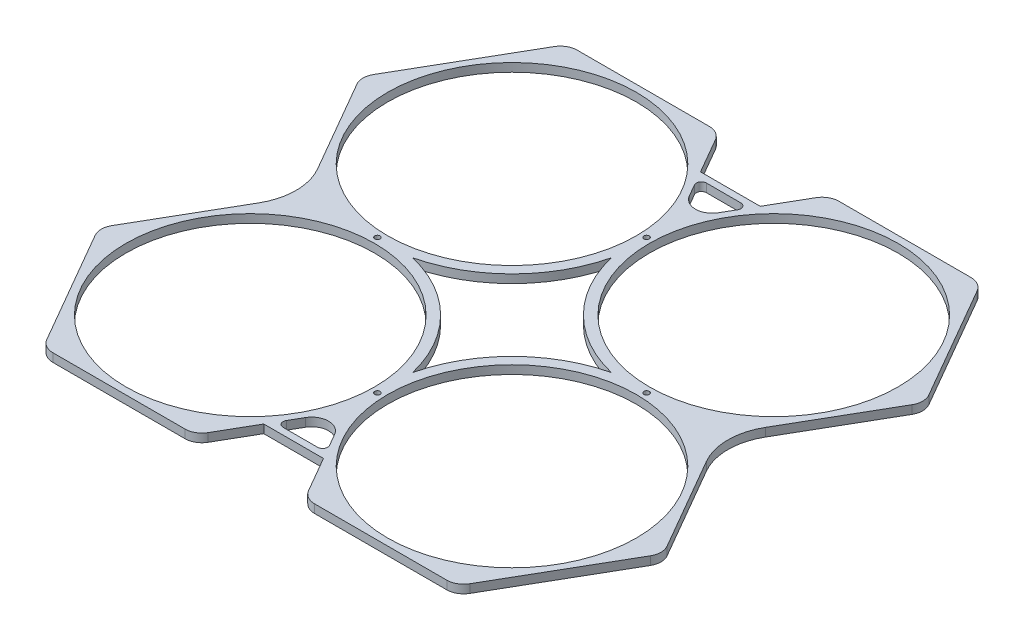
SolidWorks part; units mm, degrees
ref_plane "前视基准面" through (0, 0, 0) normal (0, 0, 1) x (1, 0, 0)
ref_plane "上视基准面" through (0, 0, 0) normal (0, 1, 0) x (1, 0, 0)
ref_plane "右视基准面" through (0, 0, 0) normal (1, 0, 0) x (0, 0, -1)
other "Configuration Table"
sketch "草图1" plane through (0, 0, 0) normal (0, 1, 0) x (1, 0, 0)
  line L0 (-40.28, 0) -> (40.28, 0) construction
  line L1 (-40.28, -50) -> (40.28, -50)
  line L2 (-40.28, -50) -> (-40.28, 50)
  line L3 (-40.28, 50) -> (40.28, 50)
  line L4 (40.28, -50) -> (40.28, 50)
  line L5 (-40.28, -50) -> (40.28, 50) construction
  line L6 (-40.28, 50) -> (40.28, -50) construction
  line L7 (0, -50) -> (0, 50) construction
  line L8 (-40.28, -50) -> (-40.28, -75.1) construction
  line L9 (-40.28, -75.1) -> (40.28, -75.1) construction
  line L10 (40.28, -75.1) -> (40.28, -50) construction
  line L11 (0, -50) -> (0, -75.1) construction
  line L12 (-40.28, -62.55) -> (40.28, -62.55) construction
  line L13 (-27, -75.1) -> (27, -75.1)
  line L14 (27, -75.1) -> (27, -50)
  line L15 (-27, -75.1) -> (-27, -50)
  circle A0 centre (-34.12, 46.89) radius 1.6
  circle A1 centre (15.09, 46.89) radius 1.6
  circle A2 centre (15.09, -40.19) radius 1.6
  circle A3 centre (-34.12, -40.19) radius 1.6
  circle A5 centre (-15.25, 15.25) radius 1.6
  circle A6 centre (15.25, 15.25) radius 1.6
  circle A7 centre (15.25, -15.25) radius 1.6
  circle A8 centre (-15.25, -15.25) radius 1.6
  circle A9 centre (14, -62.55) radius 1.6
  circle A10 centre (-14, -62.55) radius 1.6
  point P0 (0, 0)
  point P19 (0, 0)
  point P22 (0, 0)
  point P40 (0, -75.1)
  dimension "D3" = 3.2
  dimension "D10" = 3.2
  dimension "D11" = 30.5
  dimension "D12" = 30.5
  dimension "D14" = 3.2
  dimension "D1" = 80.56
  dimension "D2" = 100
  dimension "D4" = 6.16
  dimension "D5" = 3.11
  dimension "D8" = 49.21
  dimension "D9" = 87.08
  dimension "D13" = 25.1
  dimension "D15" = 28
  dimension "D16" = 54
  dimension "D6" = 2
  dimension "D7" = 2
sketch "草图6" plane through (0, 0, 0) normal (0, 1, 0) x (1, 0, 0)
  line L0 (0, 0) -> (50000, 0) construction
  line L1 (0, 0) -> (0, 50000) construction
  line L2 (-77.7817, 77.7817) -> (77.7817, 77.7817) construction
  line L3 (77.7817, 77.7817) -> (77.7817, -77.7817) construction
  line L4 (69.7817, 77.7817) -> (85.7817, 77.7817) construction
  line L5 (77.7817, 69.7817) -> (77.7817, 85.7817) construction
  line L6 (-77.7817, -77.7817) -> (77.7817, 77.7817) construction
  line L7 (77.7817, 91.5317) -> (64.0317, 77.7817)
  line L8 (91.5317, 77.7817) -> (77.7817, 64.0317)
  line L9 (-70.9067, 64.0317) -> (-40.28, 33.405)
  line L10 (-91.5317, -91.5317) -> (88.3498, 88.3498) construction
  line L11 (-87.5951, 87.5951) -> (77.7817, -77.7817) construction
  line L12 (40.28, -50) -> (40.28, 50)
  line L13 (40.28, 50) -> (-40.28, 50)
  line L14 (-40.28, 50) -> (-40.28, -50)
  line L15 (-40.28, -50) -> (40.28, -50)
  line L16 (-77.7817, 64.0317) -> (-70.9067, 64.0317)
  line L17 (-91.5317, 77.7817) -> (-77.7817, 64.0317)
  line L18 (-91.5317, 77.7817) -> (-91.5317, 85.1678)
  line L19 (-85.1678, 91.5317) -> (-91.5317, 85.1678)
  line L20 (-77.7817, 91.5317) -> (-85.1678, 91.5317)
  line L21 (77.7817, 91.5317) -> (85.1678, 91.5317)
  line L22 (91.5317, 77.7817) -> (91.5317, 85.1678)
  line L23 (-77.7817, 91.5317) -> (-64.0317, 77.7817)
  line L24 (-64.0317, 77.7817) -> (-64.0317, 70.9067)
  line L25 (72.1249, 83.4386) -> (83.4386, 72.1249) construction
  line L26 (77.7817, 64.0317) -> (70.9067, 64.0317)
  line L27 (64.0317, 77.7817) -> (64.0317, 70.9067)
  line L28 (77.7817, 64.0317) -> (70.9067, 64.0317)
  line L29 (64.0317, 77.7817) -> (64.0317, 70.9067)
  line L30 (64.0317, 70.9067) -> (40.28, 47.155)
  line L31 (70.9067, 64.0317) -> (40.28, 33.405)
  line L32 (85.1678, 91.5317) -> (91.5317, 85.1678)
  line L33 (-64.0317, 70.9067) -> (-40.28, 47.155)
  line L34 (-64.0317, -70.9067) -> (-40.28, -47.155)
  line L35 (-64.0317, -77.7817) -> (-64.0317, -70.9067)
  line L36 (-77.7817, -91.5317) -> (-64.0317, -77.7817)
  line L37 (-77.7817, -91.5317) -> (-85.1678, -91.5317)
  line L38 (-85.1678, -91.5317) -> (-91.5317, -85.1678)
  line L39 (-91.5317, -77.7817) -> (-91.5317, -85.1678)
  line L40 (-91.5317, -77.7817) -> (-77.7817, -64.0317)
  line L41 (-77.7817, -64.0317) -> (-70.9067, -64.0317)
  line L42 (-70.9067, -64.0317) -> (-40.28, -33.405)
  line L43 (70.9067, -64.0317) -> (40.28, -33.405)
  line L44 (77.7817, -64.0317) -> (70.9067, -64.0317)
  line L45 (91.5317, -77.7817) -> (77.7817, -64.0317)
  line L46 (91.5317, -77.7817) -> (91.5317, -85.1678)
  line L47 (85.1678, -91.5317) -> (91.5317, -85.1678)
  line L48 (77.7817, -91.5317) -> (85.1678, -91.5317)
  line L49 (77.7817, -91.5317) -> (64.0317, -77.7817)
  line L50 (64.0317, -77.7817) -> (64.0317, -70.9067)
  line L51 (64.0317, -70.9067) -> (40.28, -47.155)
  circle A0 centre (-77.7817, 77.7817) radius 65.9 construction
  circle A1 centre (77.7817, 77.7817) radius 65.9 construction
  circle A2 centre (-77.7817, -77.7817) radius 65.9 construction
  circle A3 centre (77.7817, -77.7817) radius 65.9 construction
  circle A4 centre (0, 0) radius 110 construction
  circle A5 centre (77.7817, 77.7817) radius 8 construction
  circle A6 centre (77.7817, 85.7817) radius 1.5
  circle A7 centre (85.7817, 77.7817) radius 1.5
  circle A8 centre (77.7817, 69.7817) radius 1.5
  circle A9 centre (69.7817, 77.7817) radius 1.5
  circle A10 centre (77.7817, 77.7817) radius 13.75 construction
  circle A11 centre (-77.7817, 85.7817) radius 1.5
  circle A12 centre (-85.7817, 77.7817) radius 1.5
  circle A13 centre (-69.7817, 77.7817) radius 1.5
  circle A14 centre (-77.7817, 69.7817) radius 1.5
  circle A15 centre (-77.7817, -69.7817) radius 1.5
  circle A16 centre (-69.7817, -77.7817) radius 1.5
  circle A17 centre (-85.7817, -77.7817) radius 1.5
  circle A18 centre (-77.7817, -85.7817) radius 1.5
  circle A19 centre (77.7817, -85.7817) radius 1.5
  circle A20 centre (85.7817, -77.7817) radius 1.5
  circle A21 centre (69.7817, -77.7817) radius 1.5
  circle A22 centre (77.7817, -69.7817) radius 1.5
  point P18 (77.7817, 77.7817)
  point P21 (77.7817, 77.7817)
  point P24 (0, 0)
  point P31 (77.7817, 77.7817)
  point P77 (77.7817, 77.7817)
sketch "草图7" plane through (0, 0, 0) normal (0, 1, 0) x (1, 0, 0)
  line L0 (0, 0) -> (50000, 0) construction
  line L1 (0, 0) -> (0, 50000) construction
  line L2 (17.7373, 129.7817) -> (-17.7373, 129.7817)
  line L3 (164.9616, 82.7817) -> (125.7018, 150.7817)
  line L4 (117.0416, 155.7817) -> (38.5219, 155.7817)
  line L5 (29.8617, 150.7817) -> (17.7373, 129.7817)
  line L8 (133.0447, 17.5) -> (164.9616, 72.7817)
  line L9 (32.7484, -0.2183) -> (122.8151, -0.2183) [skipped]
  line L10 (0, 56.5037) -> (32.7484, -0.2183) [skipped]
  line L11 (10.2318, 125.7817) -> (-10.2318, 125.7817)
  line L12 (12.8298, 121.2817) -> (8.6603, 114.0598)
  line L13 (-133.0447, 17.5) -> (-164.9616, 72.7817)
  line L14 (-164.9616, 82.7817) -> (-125.7018, 150.7817)
  line L15 (-117.0416, 155.7817) -> (-38.5219, 155.7817)
  line L16 (-29.8617, 150.7817) -> (-17.7373, 129.7817)
  line L17 (-12.8298, 121.2817) -> (-8.6603, 114.0598)
  line L18 (164.9616, -82.7817) -> (125.7018, -150.7817)
  line L19 (117.0416, -155.7817) -> (38.5219, -155.7817)
  line L20 (29.8617, -150.7817) -> (17.7373, -129.7817)
  line L21 (12.8298, -121.2817) -> (8.6603, -114.0598)
  line L22 (-12.8298, -121.2817) -> (-8.6603, -114.0598)
  line L23 (10.2318, -125.7817) -> (-10.2318, -125.7817)
  line L24 (17.7373, -129.7817) -> (-17.7373, -129.7817)
  line L25 (-29.8617, -150.7817) -> (-17.7373, -129.7817)
  line L26 (-117.0416, -155.7817) -> (-38.5219, -155.7817)
  line L27 (-164.9616, -82.7817) -> (-125.7018, -150.7817)
  line L28 (-133.0447, -17.5) -> (-164.9616, -72.7817)
  line L29 (133.0447, -17.5) -> (164.9616, -72.7817)
  line L30 (-19.75, 22.75) -> (19.75, 22.75) construction
  line L31 (-15.25, -15.25) -> (15.25, -15.25) construction
  line L32 (-15.25, -15.25) -> (-15.25, 15.25) construction
  line L33 (-15.25, 15.25) -> (15.25, 15.25) construction
  line L34 (15.25, -15.25) -> (15.25, 15.25) construction
  line L35 (-15.25, -15.25) -> (15.25, 15.25) construction
  line L36 (-15.25, 15.25) -> (15.25, -15.25) construction
  line L37 (22.75, -19.75) -> (22.75, 19.75) construction
  line L38 (-19.75, -22.75) -> (19.75, -22.75) construction
  line L39 (-22.75, -19.75) -> (-22.75, 19.75) construction
  line L40 (-22.75, 22.75) -> (22.75, 22.75) construction
  line L41 (22.75, -22.75) -> (22.75, 22.75) construction
  line L42 (-22.75, -22.75) -> (-22.75, 22.75) construction
  line L43 (-22.75, -22.75) -> (22.75, -22.75) construction
  circle A0 centre (77.7817, 77.7817) radius 78 construction
  arc A1 (164.9616, 82.7817) -> (164.9616, 72.7817) centre (156.3014, 77.7817) cw
  arc A2 (125.7018, 150.7817) -> (117.0416, 155.7817) centre (117.0416, 145.7817) ccw
  circle A3 centre (77.7817, 77.7817) radius 65.9 construction
  circle A7 centre (77.7817, 77.7817) radius 65.9 construction
  circle A8 centre (77.7817, 77.7817) radius 73.9
  arc A9 (38.5219, 155.7817) -> (29.8617, 150.7817) centre (38.5219, 145.7817) ccw
  arc A10 (133.0447, 17.5) -> (128.3556, 0) centre (163.3556, 0) ccw construction
  arc A11 (133.0447, 17.5) -> (133.0447, -17.5) centre (163.3556, 0) ccw
  circle A12 centre (0, 119.0598) radius 10 construction
  arc A13 (8.6603, 114.0598) -> (-8.6603, 114.0598) centre (0, 119.0598) cw
  circle A14 centre (-77.7817, 77.7817) radius 73.9
  arc A15 (-133.0447, 17.5) -> (-133.0447, -17.5) centre (-163.3556, 0) cw
  arc A16 (-164.9616, 82.7817) -> (-164.9616, 72.7817) centre (-156.3014, 77.7817) ccw
  arc A17 (-125.7018, 150.7817) -> (-117.0416, 155.7817) centre (-117.0416, 145.7817) cw
  arc A18 (-38.5219, 155.7817) -> (-29.8617, 150.7817) centre (-38.5219, 145.7817) cw
  circle A19 centre (-77.7817, -77.7817) radius 73.9
  circle A20 centre (77.7817, -77.7817) radius 73.9
  arc A21 (164.9616, -82.7817) -> (164.9616, -72.7817) centre (156.3014, -77.7817) ccw
  arc A22 (125.7018, -150.7817) -> (117.0416, -155.7817) centre (117.0416, -145.7817) cw
  arc A23 (8.6603, -114.0598) -> (-8.6603, -114.0598) centre (0, -119.0598) ccw
  arc A24 (-38.5219, -155.7817) -> (-29.8617, -150.7817) centre (-38.5219, -145.7817) ccw
  arc A25 (-125.7018, -150.7817) -> (-117.0416, -155.7817) centre (-117.0416, -145.7817) ccw
  arc A26 (-164.9616, -82.7817) -> (-164.9616, -72.7817) centre (-156.3014, -77.7817) cw
  arc A27 (300.0616, 4.7817) -> (300.0616, -5.2183) centre (291.4013, -0.2183) cw
  arc A28 (38.5219, -155.7817) -> (29.8617, -150.7817) centre (38.5219, -145.7817) cw
  arc A29 (-12.8298, -121.2817) -> (-10.2318, -125.7817) centre (-10.2318, -122.7817) ccw
  arc A30 (10.2318, 125.7817) -> (12.8298, 121.2817) centre (10.2318, 122.7817) cw
  arc A31 (-12.8298, 121.2817) -> (-10.2318, 125.7817) centre (-10.2318, 122.7817) cw
  arc A32 (12.8298, -121.2817) -> (10.2318, -125.7817) centre (10.2318, -122.7817) cw
  arc A33 (19.75, 22.75) -> (22.75, 19.75) centre (19.75, 19.75) cw construction
  arc A34 (-19.75, 22.75) -> (-22.75, 19.75) centre (-19.75, 19.75) ccw construction
  arc A35 (-19.75, -22.75) -> (-22.75, -19.75) centre (-19.75, -19.75) cw construction
  arc A36 (22.75, -19.75) -> (19.75, -22.75) centre (19.75, -19.75) cw construction
  point P4 (77.7817, 155.7817)
  point P21 (167.8484, 77.7817)
  point P26 (0, 0)
  point P27 (-33.5219, 154.442)
  point P33 (0, 129.7817)
  point P54 (0, 125.7817)
  point P76 (-33.5219, -154.442)
  point P100 (-15.4279, -125.7817)
  point P103 (15.4279, 125.7817)
  point P106 (-15.4279, 125.7817)
  point P109 (15.4279, -125.7817)
  dimension "D3" = 10
  dimension "D4" = 35
  dimension "D7" = 20
  dimension "D9" = 3
  dimension "D10" = 3
  dimension "D11" = 3
  dimension "D12" = 3
  dimension "D13" = 3
  dimension "D14" = 3
  dimension "D2" = 78
  dimension "D5" = 4
  dimension "D6" = 26
  dimension "D1" = 8
  dimension "D8" = 7.5
extrude "凸台-拉伸1" add sketch "草图7" along normal blind 5 contours A28 L19 A22 L18 A21 L29 A11 L8 A1 L3 A2 L4 A9 L5 L2 L16 A18 L15 A17 L14 A16 L13 A15 L28 A26 L27 A25 L26 A24 L25 L24 L20 A23 L21 L23 L22 A14 A8 L38 L39 L30 L37 L12 A13 L17 L11 region at (0, 0, 0)
sketch "草图8" plane through (0, 5, 0) normal (0, 1, 0) x (1, 0, 0)
  line L0 (-128.3556, 0) -> (128.3556, 0) construction
  line L1 (0, -129.7817) -> (0, 129.7817) construction
  line L2 (17.7373, 129.7817) -> (-17.7373, 129.7817) construction
  arc A0 (133.0447, 17.5) -> (133.0447, -17.5) centre (163.3556, 0) ccw construction
  circle A1 centre (80, 0) radius 1.6
  circle A2 centre (0, -80) radius 1.6
  circle A3 centre (-80, 0) radius 1.6
  circle A4 centre (0, 80) radius 1.6
  circle A5 centre (77.7817, 77.7817) radius 80 construction
  arc A6 (0, 59.0735) -> (59.0735, 0) centre (77.7817, 77.7817) ccw
  arc A7 (0, 59.0735) -> (-59.0735, 0) centre (-77.7817, 77.7817) cw
  arc A8 (0, -59.0735) -> (59.0735, 0) centre (77.7817, -77.7817) cw
  arc A9 (0, -59.0735) -> (-59.0735, 0) centre (-77.7817, -77.7817) ccw
  point P7 (0, 0)
  point P13 (0, 0)
  point P24 (0, 0)
  point P31 (0, 50.0365)
  dimension "D1" = 3.2
  dimension "D4" = 160
  dimension "D2" = 80
  dimension "D3" = 4
extrude "切除-拉伸1" cut sketch "草图8" against normal up to next contours A4 | A3 | A2 | A1 | A9 A8 A6 A7 region at (80, 5, 0) region at (0, 5, 80) region at (-80, 5, 0) region at (0, 5, -80) region at (0, 5, 0)
